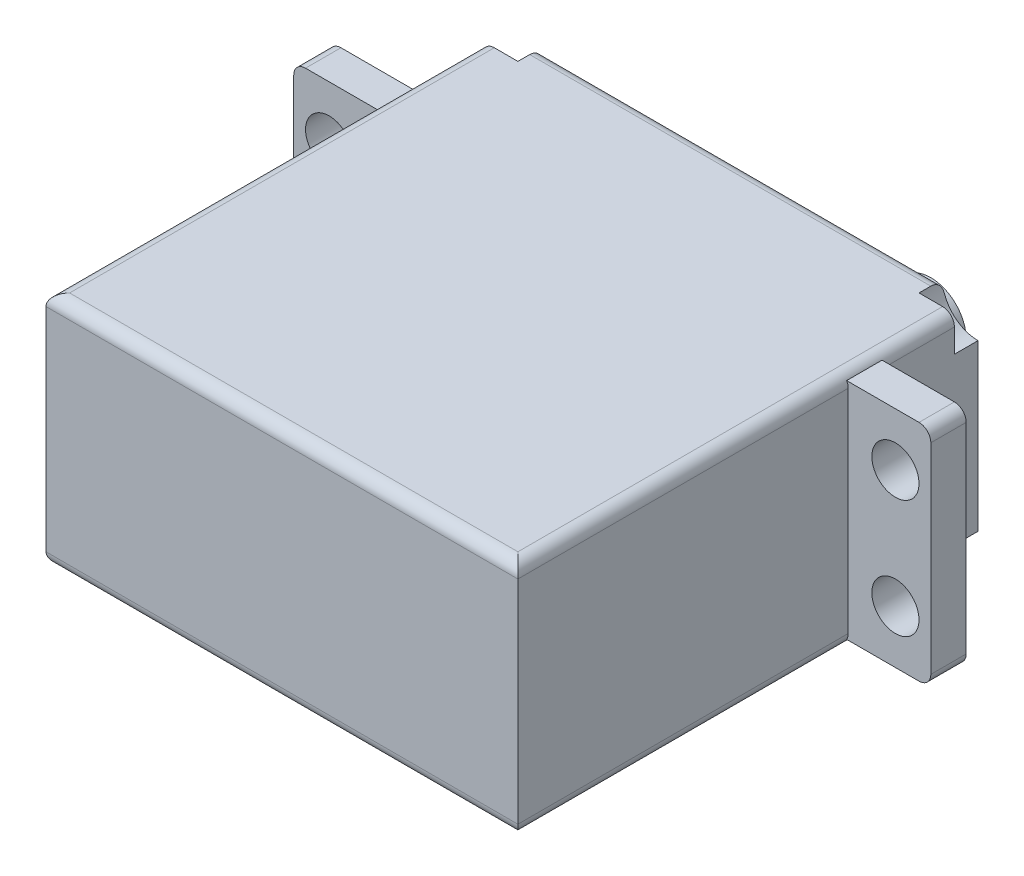
SolidWorks part; units mm, degrees
ref_plane "前视基准面" through (0, 0, 0) normal (0, 0, 1) x (1, 0, 0)
ref_plane "上视基准面" through (0, 0, 0) normal (0, 1, 0) x (1, 0, 0)
ref_plane "右视基准面" through (0, 0, 0) normal (1, 0, 0) x (0, 0, -1)
other "Configuration Table"
sketch "草图1" plane through (0, 0, 0) normal (0, 1, 0) x (1, 0, 0)
  line L1 (0, 0) -> (40, 0)
  line L2 (0, 0) -> (0, -39)
  line L3 (0, -39) -> (40, -39)
  line L4 (40, 0) -> (40, -39)
  dimension "D1" = 40
  dimension "D2" = 39
extrude "凸台-拉伸1" add sketch "草图1" along normal blind 20
sketch "草图6" plane through (0, 0, 0) normal (0, 0, -1) x (-1, 0, 0)
  line L1 (-40, 20) -> (-40, 0) construction
  circle A4 centre (-30, 10.623) radius 5
  dimension "D2" = 10
  dimension "D1" = 10
extrude "凸台-拉伸3" add sketch "草图6" along normal blind 1
sketch "草图7" plane through (0, 0, -1) normal (0, 0, -1) x (-1, 0, 0)
  circle A0 centre (-30, 10.623) radius 4.5
  dimension "D1" = 9
extrude "凸台-拉伸4" add sketch "草图7" along normal blind 0.5
sketch "草图8" plane through (0, 0, -1.5) normal (0, 0, -1) x (-1, 0, 0)
  circle A0 centre (-30, 10.623) radius 4
  dimension "D1" = 8
extrude "凸台-拉伸5" add sketch "草图8" along normal blind 0.5
sketch "草图9" plane through (0, 0, -2) normal (0, 0, -1) x (-1, 0, 0)
  circle A1 centre (-30, 10.623) radius 3
  dimension "D1" = 6
extrude "凸台-拉伸6" add sketch "草图9" along normal blind 4
ref_plane "基准面2" through (40, 20, 0) normal (0, 0, -1) x (-1, 0, 0)
sketch "草图11" plane through (40, 0, 0) normal (1, 0, 0) x (0, 0, -1)
  line L0 (-39, 20) -> (0, 20) construction
  line L1 (-11, 20) -> (-8, 20)
  line L2 (-11, 20) -> (-11, 0)
  line L3 (-11, 0) -> (-8, 0)
  line L4 (-8, 20) -> (-8, 0)
  line L5 (-39, 0) -> (0, 0) construction
  line L6 (-39, 20) -> (-39, 0) construction
  dimension "D1" = 31
  dimension "D2" = 3
extrude "凸台-拉伸7" add sketch "草图11" along normal blind 7
sketch "草图12" plane through (0, 0, 8) normal (0, 0, -1) x (-1, 0, 0)
  line L0 (-47, 20) -> (-40, 20) construction
  line L1 (-40, 20) -> (-40, 0) construction
  circle A0 centre (-44, 15) radius 2
  circle A1 centre (-44, 5) radius 2
  dimension "D4" = 4
  dimension "D5" = 4
  dimension "D1" = 10
  dimension "D2" = 5
  dimension "D3" = 4
extrude "切除-拉伸2" cut sketch "草图12" against normal blind 7
sketch "草图13" plane through (0, 0, 0) normal (-1, 0, 0) x (0, 0, 1)
  line L0 (0, 20) -> (39, 20) construction
  line L1 (8, 20) -> (11, 20)
  line L2 (8, 20) -> (8, 0)
  line L3 (8, 0) -> (11, 0)
  line L4 (11, 20) -> (11, 0)
  line L5 (0, 0) -> (39, 0) construction
  line L6 (39, 20) -> (39, 0) construction
  dimension "D1" = 31
  dimension "D2" = 3
extrude "凸台-拉伸8" add sketch "草图13" along normal blind 7
sketch "草图14" plane through (0, 0, 8) normal (0, 0, -1) x (-1, 0, 0)
  line L0 (7, 20) -> (0, 20) construction
  line L1 (0, 20) -> (0, 0) construction
  circle A0 centre (4, 15) radius 2
  circle A1 centre (4, 5) radius 2
  dimension "D1" = 4
  dimension "D2" = 4
  dimension "D3" = 10
  dimension "D4" = 5
  dimension "D5" = 4
extrude "切除-拉伸3" cut sketch "草图14" against normal blind 7
sketch "草图15" plane through (0, 0, 0) normal (0, 0, -1) x (-1, 0, 0)
  line L0 (0, 20) -> (0, 0) construction
  line L1 (-40, 20) -> (0, 20) construction
  circle A0 centre (-40, 20) radius 3
  circle A1 centre (0, 20) radius 3
  circle A2 centre (0, 0) radius 3
  circle A3 centre (-40, 0) radius 3
  dimension "D1" = 6
  dimension "D2" = 6
  dimension "D3" = 6
  dimension "D4" = 6
extrude "切除-拉伸4" cut sketch "草图15" against normal blind 2
sketch "草图16" plane through (0, 20, 0) normal (0, 1, 0) x (1, 0, 0)
  line L0 (0, -8) -> (0, -11)
extrude "切除-拉伸6" cut sketch "草图16" against normal blind 0.5 and the other way through all flip side to cut
sketch "草图17" plane through (0, 20, 0) normal (0, 1, 0) x (1, 0, 0)
  line L0 (40, -8) -> (40, -11)
extrude "切除-拉伸7" cut sketch "草图17" against normal blind 0.5 and the other way through all
sketch "草图19" plane through (0, 0, 0) normal (0, -1, 0) x (1, 0, 0)
  line L0 (0, 11) -> (0, 8)
extrude "切除-拉伸8" cut sketch "草图19" against normal blind 0.5 and the other way through all flip side to cut
sketch "草图20" plane through (0, 0, 0) normal (0, -1, 0) x (1, 0, 0)
  line L0 (40, 11) -> (40, 8)
extrude "切除-拉伸9" cut sketch "草图20" against normal blind 0.5 and the other way through all
fillet "圆角3" radius 1 12 edges at (20, 0, 39) (0, 0, 20.5) (-7, 0.5, 9.5) (20, 0, 0) (47, 0.5, 9.5) (40, 0, 20.5) (47, 19.5, 9.5) (40, 20, 20.5) (20, 20, 39) (-7, 19.5, 9.5) (20, 20, 0) (0, 20, 20.5)
